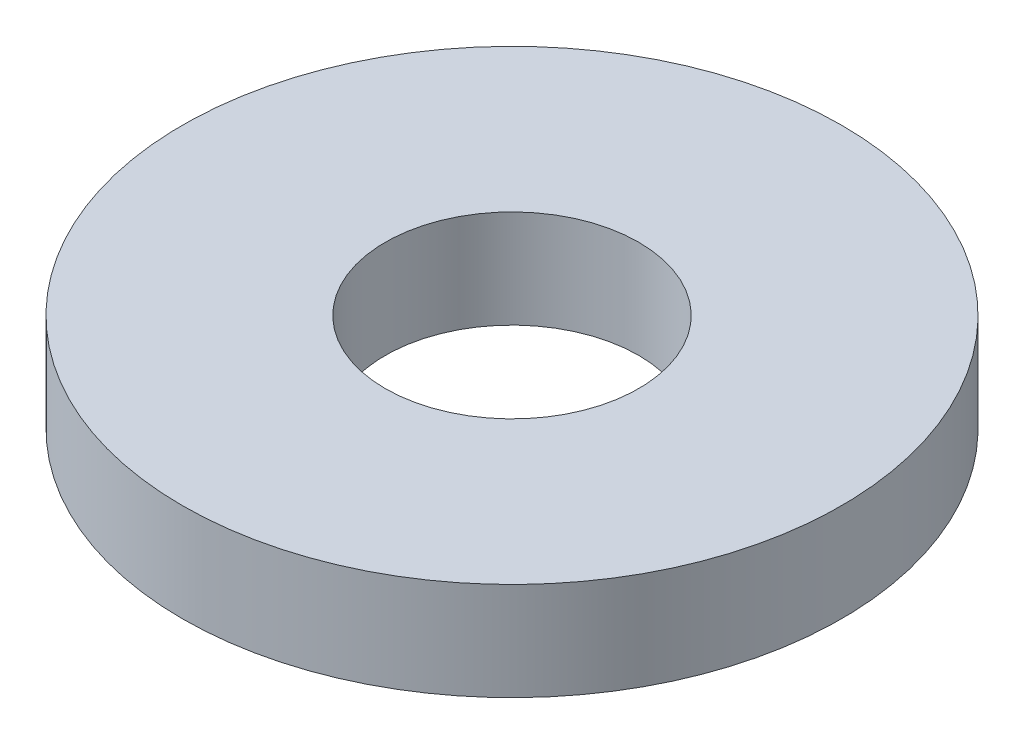
SolidWorks part; units mm, degrees
ref_plane "Front Plane" through (0, 0, 0) normal (0, 0, 1) x (1, 0, 0)
ref_plane "Top Plane" through (0, 0, 0) normal (0, 1, 0) x (1, 0, 0)
ref_plane "Right Plane" through (0, 0, 0) normal (1, 0, 0) x (0, 0, -1)
sketch "Sketch1" plane through (0, 0, 0) normal (0, 1, 0) x (1, 0, 0)
  circle A0 centre (0, 0) radius 97.5
  dimension "FLANGE_OD" = 195
extrude "Boss-Extrude1" add sketch "Sketch1" along normal blind 29
sketch "Sketch2" plane through (0, 0, 0) normal (0, 1, 0) x (1, 0, 0)
  circle A0 centre (0, 0) radius 37.5
  dimension "BORE_D" = 75
extrude "Cut-Extrude1" cut sketch "Sketch2" along normal through all
sketch "Sketch3" plane through (0, 29, 0) normal (0, 1, 0) x (1, 0, 0)
  circle A0 centre (0, 0) radius 33.0124 construction
  circle A1 centre (-33.0124, 0) radius 2.17
  dimension "BOLT_D" = 4.34
  dimension "BOLT_PCD" = 66.0247
extrude "Cut-Extrude2" cut sketch "Sketch3" against normal blind 20.9894 rebuild error yes
pattern_circular "CirPattern1" count 8 over 360 rebuild error yes
